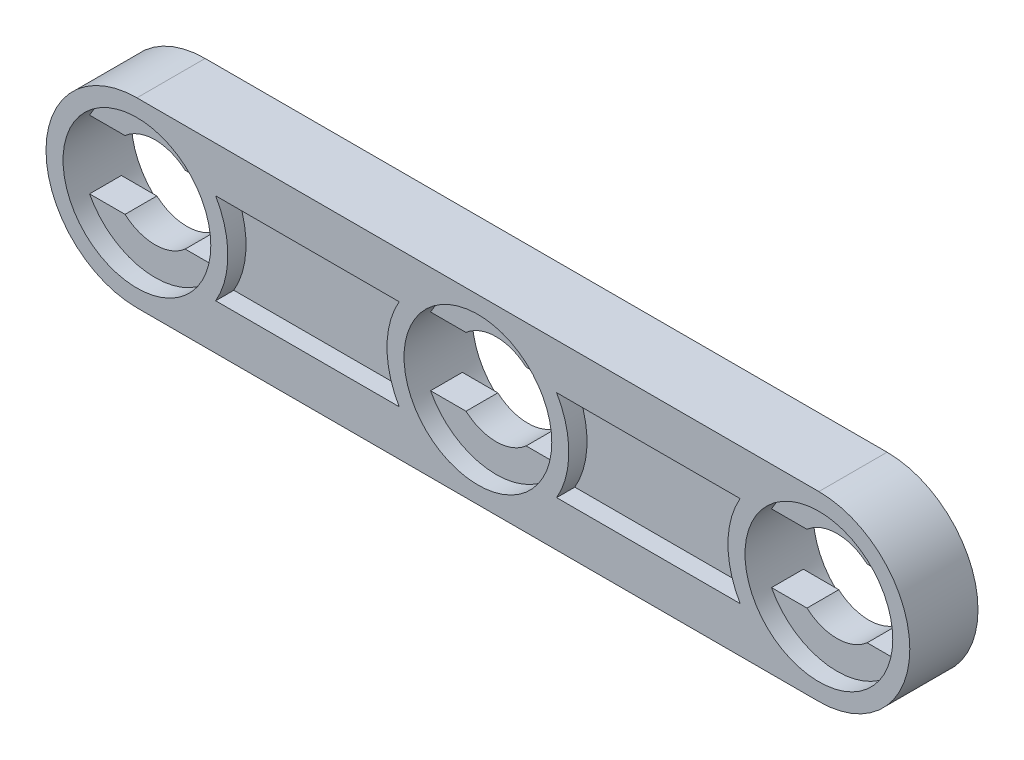
SolidWorks part; units mm, degrees
ref_plane "前视基准面" through (0, 0, 0) normal (0, 0, 1) x (1, 0, 0)
ref_plane "上视基准面" through (0, 0, 0) normal (0, 1, 0) x (1, 0, 0)
ref_plane "右视基准面" through (0, 0, 0) normal (1, 0, 0) x (0, 0, -1)
sketch "草图1" plane through (0, 0, 0) normal (0, 0, 1) x (1, 0, 0)
  line L1 (-15, -4) -> (15, -4)
  line L3 (-15, 4) -> (15, 4)
  arc A0 (-15, 4) -> (-15, -4) centre (-15, 0) ccw
  arc A1 (15, -4) -> (15, 4) centre (15, 0) ccw
extrude "凸台-拉伸1" add sketch "草图1" against normal blind 3
sketch "草图2" plane through (0, 0, 0) normal (0, 0, 1) x (1, 0, 0)
  line L0 (-2.8831, -1.5) -> (-1.3229, -1.5)
  line L1 (-17.8831, 1.5) -> (-16.3229, 1.5)
  line L2 (-2.8831, 1.5) -> (-1.3229, 1.5)
  line L3 (-17.8831, -1.5) -> (-16.3229, -1.5)
  line L4 (12.1169, 1.5) -> (13.6771, 1.5)
  line L5 (-13.6771, 1.5) -> (-12.1169, 1.5)
  line L6 (-13.6771, -1.5) -> (-12.1169, -1.5)
  line L7 (1.3229, -1.5) -> (2.8831, -1.5)
  line L8 (1.3229, 1.5) -> (2.8831, 1.5)
  line L9 (16.3229, 1.5) -> (17.8831, 1.5)
  line L10 (16.3229, -1.5) -> (17.8831, -1.5)
  line L11 (12.1169, -1.5) -> (13.6771, -1.5)
  arc A0 (-17.8831, 1.5) -> (-17.8831, -1.5) centre (-15, 0) ccw
  arc A1 (2.8831, -1.5) -> (2.8831, 1.5) centre (0, 0) ccw
  arc A2 (17.8831, -1.5) -> (17.8831, 1.5) centre (15, 0) ccw
  arc A3 (-16.3229, -1.5) -> (-13.6771, -1.5) centre (-15, 0) ccw
  arc A4 (-1.3229, -1.5) -> (1.3229, -1.5) centre (0, 0) ccw
  arc A5 (13.6771, -1.5) -> (16.3229, -1.5) centre (15, 0) ccw
  arc A6 (-13.6771, 1.5) -> (-16.3229, 1.5) centre (-15, 0) ccw
  arc A7 (-12.1169, -1.5) -> (-12.1169, 1.5) centre (-15, 0) ccw
  arc A8 (1.3229, 1.5) -> (-1.3229, 1.5) centre (0, 0) ccw
  arc A9 (-2.8831, 1.5) -> (-2.8831, -1.5) centre (0, 0) ccw
  arc A10 (16.3229, 1.5) -> (13.6771, 1.5) centre (15, 0) ccw
  arc A11 (12.1169, 1.5) -> (12.1169, -1.5) centre (15, 0) ccw
extrude "切除-拉伸1" cut sketch "草图2" against normal up to next
sketch "草图3" plane through (0, 0, 0) normal (0, 0, 1) x (1, 0, 0)
  circle A0 centre (-15, 0) radius 3.25
  circle A1 centre (0, 0) radius 3.25
  circle A2 centre (15, 0) radius 3.25
extrude "切除-拉伸2" cut sketch "草图3" against normal blind 0.8
extrude "切除-拉伸3" cut sketch "草图3<2>" along normal blind 0.8 from offset 3 offset against normal yes
sketch "草图3<2>" plane through (0, 0, 0) normal (0, 0, 1) x (1, 0, 0) same geometry as "草图3"
sketch "草图4" plane through (0, 0, 0) normal (0, 0, 1) x (1, 0, 0)
  line L0 (-11.5359, 2) -> (-3.4641, 2)
  line L1 (3.4641, 2) -> (11.5359, 2)
  line L2 (3.4641, -2) -> (11.5359, -2)
  line L5 (-11.5359, -2) -> (-3.4641, -2)
  arc A0 (3.4641, -2) -> (3.4641, 2) centre (0, 0) ccw
  arc A1 (-3.4641, 2) -> (-3.4641, -2) centre (0, 0) ccw
  arc A2 (11.5359, 2) -> (11.5359, -2) centre (15, 0) ccw
  arc A3 (-11.5359, -2) -> (-11.5359, 2) centre (-15, 0) ccw
extrude "切除-拉伸4" cut sketch "草图4" against normal blind 0.8
extrude "切除-拉伸5" cut sketch "草图4<2>" along normal blind 0.8 from offset 3 offset against normal yes
sketch "草图4<2>" plane through (0, 0, 0) normal (0, 0, 1) x (1, 0, 0) same geometry as "草图4"
